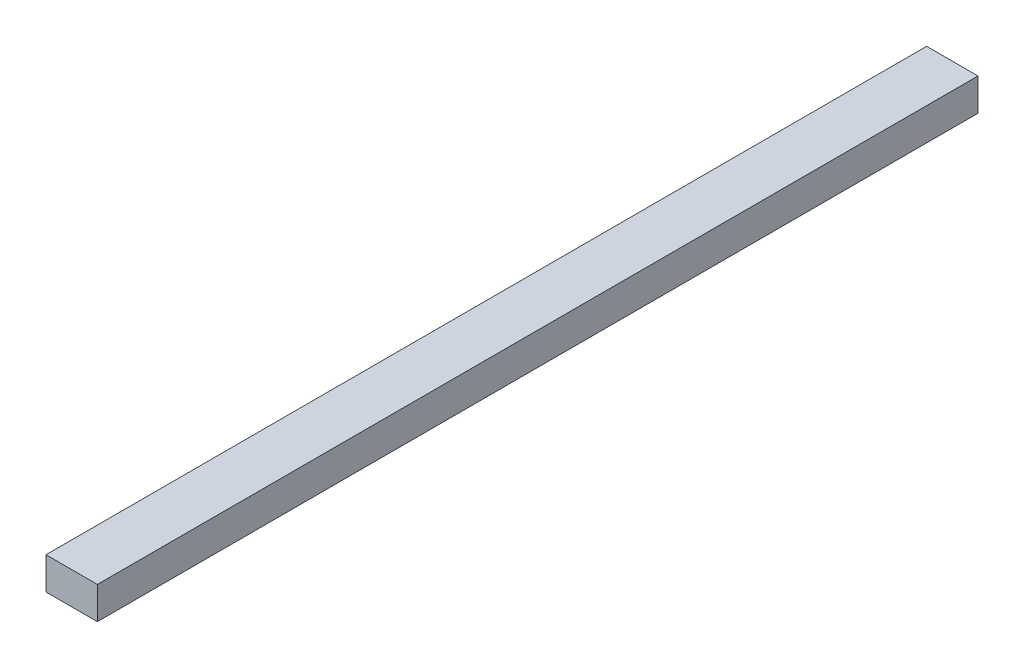
SolidWorks part; units mm, degrees
ref_plane "Front Plane" through (0, 0, 0) normal (0, 0, 1) x (1, 0, 0)
ref_plane "Top Plane" through (0, 0, 0) normal (0, 1, 0) x (1, 0, 0)
ref_plane "Right Plane" through (0, 0, 0) normal (1, 0, 0) x (0, 0, -1)
sketch "Sketch1" plane through (0, 0, 0) normal (0, 0, 1) x (1, 0, 0)
  line L7 (-35, -22) -> (35, -22)
  line L8 (-35, -22) -> (-35, 22)
  line L9 (-35, 22) -> (35, 22)
  line L10 (35, -22) -> (35, 22)
  line L11 (-35, -22) -> (35, 22) construction
  line L12 (-35, 22) -> (35, -22) construction
  point P10 (0, 0)
  dimension "D1" = 70
  dimension "D2" = 44
extrude "Boss-Extrude1" add sketch "Sketch1" along normal blind 600 and the other way blind 600
